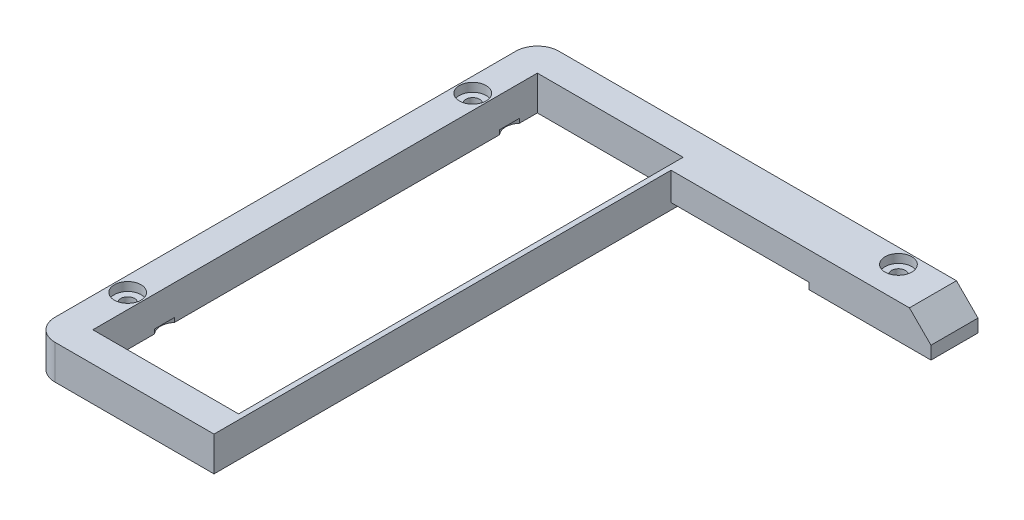
SolidWorks part; units mm, degrees
ref_plane "前视基准面" through (0, 0, 0) normal (0, 0, 1) x (1, 0, 0)
ref_plane "上视基准面" through (0, 0, 0) normal (0, 1, 0) x (1, 0, 0)
ref_plane "右视基准面" through (0, 0, 0) normal (1, 0, 0) x (0, 0, -1)
other "Configuration Table"
sketch "草图1" plane through (0, 0, 0) normal (0, 1, 0) x (1, 0, 0)
  line L1 (0, 0) -> (337.35, 0)
  line L2 (0, 0) -> (0, 116.87)
  line L3 (0, 116.87) -> (337.35, 116.87)
  line L4 (337.35, 0) -> (337.35, 116.87)
  line L5 (6.9, 109.97) -> (330.95, 109.97)
  line L6 (6.9, 109.97) -> (6.9, 6.9)
  line L7 (6.9, 6.9) -> (330.95, 6.9)
  line L8 (330.95, 109.97) -> (330.95, 6.9)
  dimension "D1" = 116.87
  dimension "D2" = 337.35
  dimension "D3" = 6.9
  dimension "D4" = 6.4
  dimension "D5" = 6.9
  dimension "D6" = 6.9
extrude "凸台-拉伸1" add sketch "草图1" along normal blind 8
fillet "圆角1" radius 5 4 edges at (0, 4, 0) (0, 4, -116.87) (337.35, 4, -116.87) (337.35, 4, 0)
sketch "草图2" plane through (0, 8, 0) normal (0, 1, 0) x (1, 0, 0)
  line L0 (167.17, 132.4281) -> (167.17, -13.3473) construction
  line L1 (0, 58.435) -> (337.35, 58.435) construction
  line L2 (0, 111.87) -> (0, 5) construction
  line L3 (337.35, 5) -> (337.35, 111.87) construction
  line L4 (23.7897, 113.42) -> (281.2218, 113.42) construction
  line L5 (3.45, 113.0437) -> (3.45, 3.45) construction
  line L6 (3.45, 3.45) -> (334.15, 3.45) construction
  line L7 (334.15, 3.45) -> (334.15, 110.0858) construction
  line L8 (332.35, 116.87) -> (5, 116.87) construction
  line L9 (330.95, 109.97) -> (6.9, 109.97) construction
  line L10 (6.9, 109.97) -> (6.9, 6.9) construction
  line L11 (6.9, 6.9) -> (330.95, 6.9) construction
  line L12 (5, 0) -> (332.35, 0) construction
  line L13 (330.95, 6.9) -> (330.95, 109.97) construction
  point P26 (87.17, 113.42)
  point P27 (247.17, 113.42)
  point P28 (247.17, 3.45)
  point P29 (87.17, 3.45)
  point P30 (3.45, 18.435)
  point P31 (334.15, 98.435)
  point P32 (3.45, 98.435)
  point P33 (334.15, 18.435)
  dimension "D1" = 167.17
  dimension "D2" = 160
  dimension "D3" = 80
hole_wizard "Ø3.2 (3.2) 直径孔1" positions "草图3" profile "草图4" hole size "Ø3.2" standard "ANSI Metric" end condition through all
sketch "草图3" plane through (0, 8, 0) normal (0, 1, 0) x (1, 0, 0)
  point P0 (3.45, 98.435)
  point P3 (87.17, 113.42)
  point P6 (247.17, 113.42)
  point P9 (334.15, 98.435)
  point P12 (334.15, 18.435)
  point P15 (247.17, 3.45)
  point P18 (87.17, 3.45)
  point P21 (3.45, 18.435)
sketch "草图4" plane through (3.45, 8, -98.435) normal (1, 0, 0) x (0, 0, 1)
  line L0 (0, 0) -> (0, 8)
  line L1 (0, 8) -> (1.6, 8)
  line L2 (1.6, 8) -> (1.6, 0)
  line L5 (1.6, 0) -> (0, 0)
  line L11 (0, -6.35) -> (0, 107.95) construction
  dimension "通孔孔直径" = 3.2
  dimension "通孔孔深度" = 8
sketch "草图5" plane through (0, 0, -109.97) normal (0, 0, 1) x (1, 0, 0)
  line L0 (330.95, 0) -> (6.9, 0) construction
  line L1 (41.9, 0) -> (73.9, 0)
  line L2 (41.9, 0) -> (41.9, 1.5)
  line L3 (41.9, 1.5) -> (73.9, 1.5)
  line L4 (73.9, 0) -> (73.9, 1.5)
  line L5 (6.9, 8) -> (6.9, 0) construction
  dimension "D1" = 35
  dimension "D2" = 32
  dimension "D3" = 1.5
extrude "切除-拉伸1" cut sketch "草图5" against normal through all
sketch "草图6" plane through (0, 0, -109.97) normal (0, 0, 1) x (1, 0, 0)
  line L0 (330.95, 8) -> (6.9, 8) construction
  line L1 (41.9, 0) -> (38.9, 0)
  line L2 (41.9, 0) -> (41.9, 8)
  line L3 (41.9, 8) -> (38.9, 8)
  line L4 (38.9, 0) -> (38.9, 8)
  dimension "D1" = 3
extrude "凸台-拉伸2" add sketch "草图6" along normal up to next
sketch "草图7" plane through (0, 0, -109.97) normal (0, 0, 1) x (1, 0, 0)
  line L1 (73.9, 0) -> (330.95, 0)
  line L2 (73.9, 0) -> (73.9, 8)
  line L3 (73.9, 8) -> (330.95, 8)
  line L4 (330.95, 0) -> (330.95, 8)
extrude "凸台-拉伸3" add sketch "草图7" along normal blind 4
sketch "草图8" plane through (0, 0, 0) normal (0, -1, 0) x (1, 0, 0)
  line L1 (330.95, -105.97) -> (73.9, -105.97)
  line L2 (330.95, -105.97) -> (330.95, -109.97)
  line L3 (330.95, -109.97) -> (73.9, -109.97)
  line L4 (73.9, -105.97) -> (73.9, -109.97)
extrude "凸台-拉伸4" add sketch "草图8" along normal blind 3
sketch "草图9" plane through (0, 8, 0) normal (0, 1, 0) x (1, 0, 0)
  circle A0 centre (137.8085, 107.33) radius 3.5
  circle A1 centre (328.3085, 74.31) radius 3.5
  circle A2 centre (328.3085, 13.35) radius 3.5
  circle A3 centre (262.2685, 9.54) radius 3.5
  circle A4 centre (92.0885, 9.54) radius 3.5
  circle A5 centre (22.2385, 9.54) radius 3.5
  circle A6 centre (9.5385, 23.51) radius 3.5
  circle A7 centre (9.5385, 103.52) radius 3.5
  dimension "D1" = 7
sketch "草图11" plane through (330.95, 0, 0) normal (-1, 0, 0) x (0, 0, 1)
  line L1 (-6.9, 8) -> (-105.97, 8)
  line L2 (-6.9, 8) -> (-6.9, -3)
  line L3 (-6.9, -3) -> (-105.97, -3)
  line L4 (-105.97, 8) -> (-105.97, -3)
extrude "凸台-拉伸5" add sketch "草图11" along normal blind 2
sketch "草图13" plane through (0, 0, -105.97) normal (0, 0, 1) x (1, 0, 0)
  line L0 (328.95, 8) -> (73.9, 8) construction
  line L1 (328.95, -3) -> (286.95, -3)
  line L2 (328.95, -3) -> (328.95, 1.5)
  line L3 (328.95, 1.5) -> (286.95, 1.5)
  line L4 (286.95, -3) -> (286.95, 1.5)
  dimension "D1" = 6.5
  dimension "D2" = 42
extrude "切除-拉伸2" cut sketch "草图13" against normal through all
sketch "草图14" plane through (0, 0, -6.9) normal (0, 0, -1) x (-1, 0, 0)
  line L0 (-41.9, 0) -> (-328.95, 0) construction
  line L1 (-233.95, 0) -> (-112.45, 0)
  line L2 (-233.95, 0) -> (-233.95, 1.5)
  line L3 (-233.95, 1.5) -> (-112.45, 1.5)
  line L4 (-112.45, 0) -> (-112.45, 1.5)
  line L6 (-41.9, 8) -> (-328.95, 8) construction
  line L7 (-328.95, 0) -> (-328.95, 8) construction
  dimension "D1" = 6.5
  dimension "D2" = 95
  dimension "D3" = 216.5
extrude "切除-拉伸3" cut sketch "草图14" against normal through all
sketch "草图16" plane through (0, 0, -109.97) normal (0, 0, 1) x (1, 0, 0)
  line L1 (41.9, 8) -> (73.9, 8)
  line L2 (41.9, 8) -> (41.9, 1.5)
  line L3 (41.9, 1.5) -> (73.9, 1.5)
  line L4 (73.9, 8) -> (73.9, 1.5)
extrude "凸台-拉伸7" add sketch "草图16" along normal up to surface (4 mm away) up to face at (229.9333, 2.1667, -105.97)
sketch "草图17" plane through (330.95, 0, 0) normal (1, 0, 0) x (0, 0, -1)
  line L8 (109.97, -3) -> (109.97, 0)
  line L9 (109.97, 0) -> (6.9, 0)
  line L10 (6.9, 0) -> (6.9, -3)
  line L11 (6.9, -3) -> (109.97, -3)
  line L12 (109.97, -3) -> (109.97, 0)
  line L13 (109.97, 0) -> (6.9, 0)
  line L14 (6.9, 0) -> (6.9, -3)
  line L15 (6.9, -3) -> (109.97, -3)
  dimension "D1" = 0
extrude "切除-拉伸4" cut sketch "草图17" against normal blind 0.1
sketch "草图18" plane through (0, 0, -6.9) normal (0, 0, -1) x (-1, 0, 0)
  line L16 (-233.95, 0) -> (-233.95, 1.5)
  line L17 (-233.95, 1.5) -> (-112.45, 1.5)
  line L18 (-112.45, 1.5) -> (-112.45, 0)
  line L19 (-112.45, 0) -> (-41.9, 0)
  line L20 (-41.9, 0) -> (-41.9, 8)
  line L21 (-41.9, 8) -> (-328.95, 8)
  line L22 (-328.95, 8) -> (-328.95, 0)
  line L23 (-328.95, 0) -> (-233.95, 0)
  line L24 (-233.95, 0) -> (-233.95, 1.5)
  line L25 (-233.95, 1.5) -> (-112.45, 1.5)
  line L26 (-112.45, 1.5) -> (-112.45, 0)
  line L27 (-112.45, 0) -> (-41.9, 0)
  line L28 (-41.9, 0) -> (-41.9, 8)
  line L29 (-41.9, 8) -> (-328.95, 8)
  line L30 (-328.95, 8) -> (-328.95, 0)
  line L31 (-328.95, 0) -> (-233.95, 0)
  dimension "D1" = 0
extrude "凸台-拉伸8" add sketch "草图18" along normal blind 2
sketch "草图19" plane through (0, 0, 0) normal (0, -1, 0) x (1, 0, 0)
  line L0 (112.45, 0) -> (112.45, -8.9) construction
  line L1 (41.9, -8.9) -> (112.45, -8.9)
  line L2 (41.9, -8.9) -> (41.9, -6.9)
  line L3 (41.9, -6.9) -> (112.45, -6.9)
  line L4 (112.45, -8.9) -> (112.45, -6.9)
  line L6 (233.95, -8.9) -> (328.95, -8.9)
  line L7 (233.95, -8.9) -> (233.95, -6.9)
  line L8 (233.95, -6.9) -> (328.95, -6.9)
  line L9 (328.95, -8.9) -> (328.95, -6.9)
  dimension "D1" = 2
extrude "凸台-拉伸9" add sketch "草图19" along normal up to surface (3 mm away) up to face at (329.9, -3, -58.435)
sketch "草图10" plane through (0, -3, 0) normal (0, -1, 0) x (1, 0, 0)
  circle A2 centre (137.8085, -107.33) radius 3.5
  circle A3 centre (137.8085, -107.33) radius 3.5
  dimension "D1" = 0
sketch "草图20" plane through (0, -3, 0) normal (0, -1, 0) x (1, 0, 0)
  circle A58 centre (92.0885, -9.54) radius 3.5
  circle A59 centre (92.0885, -9.54) radius 3.5
  circle A120 centre (262.2685, -9.54) radius 3.5
  circle A121 centre (262.2685, -9.54) radius 3.5
  circle A123 centre (328.3085, -13.35) radius 3.5
  circle A124 centre (328.3085, -13.35) radius 3.5
  circle A126 centre (328.3085, -74.31) radius 3.5
  circle A127 centre (328.3085, -74.31) radius 3.5
  circle A129 centre (137.8085, -107.33) radius 3.5
  circle A130 centre (137.8085, -107.33) radius 3.5
  circle A132 centre (22.2385, -9.54) radius 3.5
  circle A133 centre (22.2385, -9.54) radius 3.5
  circle A135 centre (9.5385, -23.51) radius 3.5
  circle A136 centre (9.5385, -23.51) radius 3.5
  circle A138 centre (9.5385, -103.52) radius 3.5
  circle A139 centre (9.5385, -103.52) radius 3.5
  dimension "D1" = 0
  dimension "D2" = 0
  dimension "D3" = 0
  dimension "D4" = 0
  dimension "D5" = 0
  dimension "D6" = 0
  dimension "D7" = 0
  dimension "D8" = 0
extrude "切除-拉伸5" cut sketch "草图20" against normal blind 4
sketch "草图21" plane through (0, 8, 0) normal (0, 1, 0) x (1, 0, 0)
  circle A2 centre (87.17, 113.42) radius 3.1
  circle A3 centre (87.17, 113.42) radius 3.1
  circle A5 centre (247.17, 113.42) radius 3.1
  circle A6 centre (247.17, 113.42) radius 3.1
  circle A8 centre (334.15, 98.435) radius 3.1
  circle A9 centre (334.15, 98.435) radius 3.1
  circle A11 centre (334.15, 18.435) radius 3.1
  circle A12 centre (334.15, 18.435) radius 3.1
  circle A14 centre (247.17, 3.45) radius 3.1
  circle A15 centre (247.17, 3.45) radius 3.1
  circle A17 centre (87.17, 3.45) radius 3.1
  circle A18 centre (87.17, 3.45) radius 3.1
  circle A20 centre (3.45, 18.435) radius 3.1
  circle A21 centre (3.45, 18.435) radius 3.1
  circle A23 centre (3.45, 98.435) radius 3.1
  circle A24 centre (3.45, 98.435) radius 3.1
  dimension "D1" = 1.5
  dimension "D2" = 1.5
  dimension "D3" = 1.5
  dimension "D4" = 1.5
  dimension "D5" = 1.5
  dimension "D6" = 1.5
  dimension "D7" = 1.5
  dimension "D8" = 1.5
extrude "切除-拉伸6" cut sketch "草图21" against normal blind 2
ref_plane "基准面1" through (0, 4, 0) normal (0, 1, 0) x (1, 0, 0)
sketch "草图22" plane through (0, 4, 0) normal (0, 1, 0) x (1, 0, 0)
  line L0 (6.9, 106.97) -> (12.9, 106.97) construction
  line L1 (6.9, 109.97) -> (12.9, 109.97)
  line L2 (6.9, 109.97) -> (6.9, 103.97)
  line L3 (6.9, 103.97) -> (12.9, 103.97)
  line L4 (12.9, 109.97) -> (12.9, 103.97)
  line L5 (38.9, 109.97) -> (32.9, 109.97)
  line L6 (38.9, 109.97) -> (38.9, 103.97)
  line L7 (38.9, 103.97) -> (32.9, 103.97)
  line L8 (32.9, 109.97) -> (32.9, 103.97)
  line L9 (6.9, 6.9) -> (12.9, 6.9)
  line L10 (6.9, 6.9) -> (6.9, 12.9)
  line L11 (6.9, 12.9) -> (12.9, 12.9)
  line L12 (12.9, 6.9) -> (12.9, 12.9)
  line L13 (38.9, 6.9) -> (32.9, 6.9)
  line L14 (38.9, 6.9) -> (38.9, 12.9)
  line L15 (38.9, 12.9) -> (32.9, 12.9)
  line L16 (32.9, 6.9) -> (32.9, 12.9)
  line L17 (32.9, 106.97) -> (38.9, 106.97) construction
  line L18 (6.9, 9.9) -> (12.9, 9.9) construction
  line L19 (32.9, 9.9) -> (38.9, 9.9) construction
  circle A0 centre (9.9, 106.97) radius 2.15
  circle A1 centre (35.9, 106.97) radius 2.15
  circle A2 centre (9.9, 9.9) radius 2.15
  circle A3 centre (35.9, 9.9) radius 2.15
  dimension "D2" = 4.3
  dimension "D1" = 6
sketch "草图23" plane through (0, 0, 0) normal (-1, 0, 0) x (0, 0, 1)
  line L0 (-111.87, 0) -> (-5, 0) construction
  line L1 (-58.435, 0) -> (-43.435, 0)
  line L2 (-58.435, 0) -> (-58.435, 1.5)
  line L3 (-58.435, 1.5) -> (-43.435, 1.5)
  line L4 (-43.435, 0) -> (-43.435, 1.5)
  line L6 (-58.435, 0) -> (-68.435, 0)
  line L7 (-58.435, 0) -> (-58.435, 1.5)
  line L8 (-58.435, 1.5) -> (-68.435, 1.5)
  line L9 (-68.435, 0) -> (-68.435, 1.5)
  dimension "D1" = 1.5
  dimension "D2" = 15
  dimension "D3" = 10
sketch "草图24" plane through (337.35, 0, 0) normal (1, 0, 0) x (0, 0, -1)
  line L1 (6.9, 0) -> (109.97, 0)
  line L2 (6.9, 0) -> (6.9, -3)
  line L3 (6.9, -3) -> (109.97, -3)
  line L4 (109.97, 0) -> (109.97, -3)
extrude "切除-拉伸8" cut sketch "草图24" against normal through all
sketch "草图25" plane through (0, 8, 0) normal (0, 1, 0) x (1, 0, 0)
  line L1 (232.17, 117.9857) -> (345.6852, 117.9857)
  line L2 (232.17, 117.9857) -> (232.17, 83.435)
  line L3 (232.17, 83.435) -> (345.6852, 83.435)
  line L4 (345.6852, 117.9857) -> (345.6852, 83.435)
  line L5 (-28.704, 160.2755) -> (437.7923, 160.2755)
  line L6 (-28.704, 160.2755) -> (-28.704, -43.3563)
  line L7 (-28.704, -43.3563) -> (437.7923, -43.3563)
  line L8 (437.7923, 160.2755) -> (437.7923, -43.3563)
  dimension "D1" = 15
  dimension "D2" = 15
sketch "草图26" plane through (0, 8, 0) normal (0, 1, 0) x (1, 0, 0)
  line L0 (332.35, 116.87) -> (5, 116.87) construction
  line L1 (0, 116.87) -> (102.17, 116.87)
  line L2 (0, 116.87) -> (0, 0)
  line L3 (0, 0) -> (41.9, 0)
  line L4 (102.17, 116.87) -> (102.17, 8.9)
  line L5 (41.9, 8.9) -> (102.17, 8.9)
  line L6 (41.9, 8.9) -> (41.9, 0)
  line L9 (0, 111.87) -> (0, 5) construction
  line L10 (5, 0) -> (332.35, 0) construction
  line L12 (-151.0524, 262.8371) -> (524.8215, 262.8371)
  line L13 (-151.0524, 262.8371) -> (-151.0524, -89.0377)
  line L14 (-151.0524, -89.0377) -> (524.8215, -89.0377)
  line L15 (524.8215, 262.8371) -> (524.8215, -89.0377)
  dimension "D1" = 15
extrude "切除-拉伸9" cut sketch "草图26" against normal through all
chamfer "倒角1" distance 5 angle 45 1 edges at (102.17, 8, -111.42)
sketch "草图27" plane through (0, 8, 0) normal (0, 1, 0) x (1, 0, 0)
  line L0 (6.9, 6.9) -> (38.9, 6.9) construction
  line L1 (38.9, 109.97) -> (40.7, 109.97)
  line L2 (38.9, 109.97) -> (38.9, 6.9)
  line L3 (38.9, 6.9) -> (40.7, 6.9)
  line L4 (40.7, 109.97) -> (40.7, 6.9)
  line L5 (38.9, 109.97) -> (40.7, 6.9) construction
  line L6 (38.9, 6.9) -> (40.7, 109.97) construction
  line L7 (41.9, 0) -> (41.9, 105.97) construction
  point P4 (39.8, 58.435)
  dimension "D1" = 1.2
extrude "切除-拉伸10" cut sketch "草图27" against normal through all
